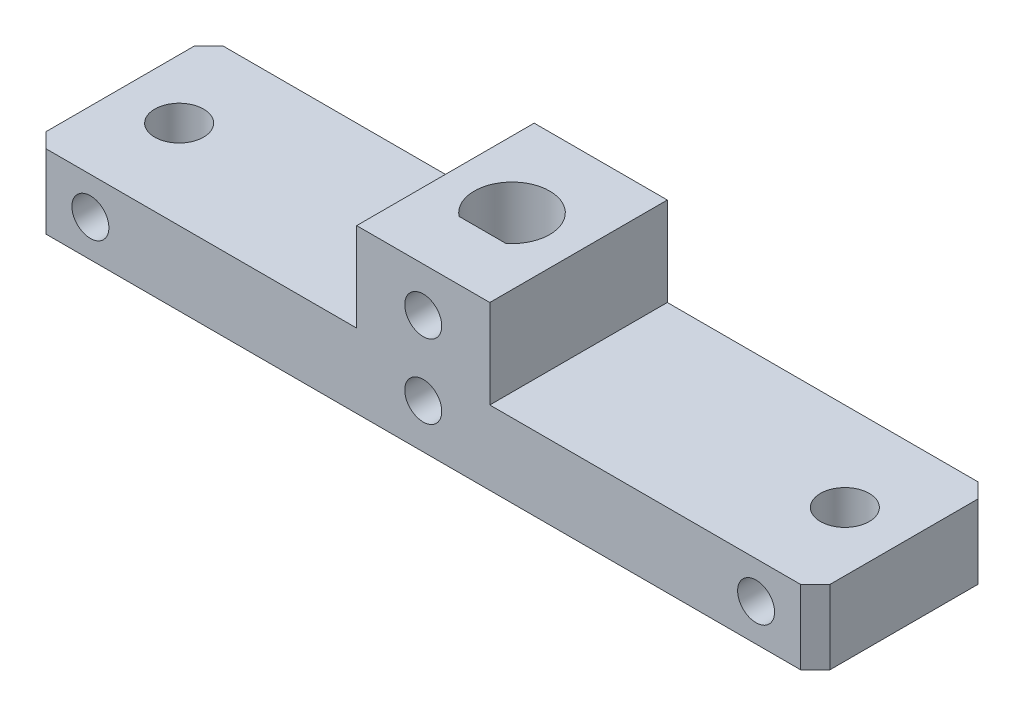
SolidWorks part; units mm, degrees
ref_plane "Top" through (0, 0, 0) normal (0, 0, 1) x (1, 0, 0)
ref_plane "Front" through (0, 0, 0) normal (0, 1, 0) x (1, 0, 0)
ref_plane "Right" through (0, 0, 0) normal (1, 0, 0) x (0, 0, -1)
sketch "Body Sketch" plane through (0, 0, 0) normal (0, 0, 1) x (1, 0, 0)
  line L0 (-26.5, 0) -> (26.5, 0)
  line L1 (26.5, 0) -> (26.5, 5)
  line L2 (26.5, 5) -> (4.5, 5)
  line L3 (4.5, 5) -> (4.5, 11)
  line L4 (4.5, 11) -> (-4.5, 11)
  line L5 (-4.5, 11) -> (-4.5, 5)
  line L6 (-4.5, 5) -> (-26.5, 5)
  line L7 (-26.5, 5) -> (-26.5, 0)
  point P8 (0, 0)
  dimension "D1" = 53
  dimension "D2" = 9
  dimension "D3" = 5
  dimension "D4" = 6
extrude "Body Extrude" add sketch "Body Sketch" against normal blind 12
sketch "Sketch2" plane through (0, 0, 0) normal (0, 1, 0) x (1, 0, 0)
  line L0 (-22.5, 6) -> (22.5, 6) construction
  line L1 (-1.5819, 4) -> (1.5819, 4)
  line L2 (0, 4) -> (0, 8.55) construction
  arc A2 (1.5819, 4) -> (-1.5819, 4) centre (0, 6) ccw
  point P8 (0, 6)
  dimension "D3" = 5.1
  dimension "D1" = 6
  dimension "D2" = 45
  dimension "D4" = 4.55
hole_wizard "M4x0.7 Tapped Hole6" positions "Sketch5" profile "Sketch6" tap size "M4x0.7" standard "ANSI Metric" end condition up to next
sketch "Sketch5" plane through (0, 0, 0) normal (0, 1, 0) x (1, 0, 0)
  line L0 (-22.5, 6) -> (22.5, 6) construction
  line L2 (0, 0) -> (0, 6) construction
  point P0 (-22.5, 6)
  point P2 (22.5, 6)
  dimension "D1" = 45
  dimension "D2" = 6
cosmetic thread "Hole Thread1"
cosmetic thread "Hole Thread2"
sketch "Sketch6" plane through (-22.5, 0, -6) normal (1, 0, 0) x (0, 0, -1)
  line L0 (0, 0) -> (0, 5)
  line L1 (0, 5) -> (1.65, 5)
  line L2 (1.65, 5) -> (1.65, 0)
  line L5 (1.65, 0) -> (0, 0)
  line L11 (0, -6.35) -> (0, 107.95) construction
  dimension "Thru Tap Drill Dia." = 3.3
  dimension "Thru Tap Drill Depth" = 5
extrude "Cut-Extrude1" cut sketch "Sketch2" along normal through all
hole_wizard "M3x0.5 Tapped Hole1" positions "Sketch7" profile "Sketch8" tap size "M3x0.5" standard "ANSI Metric" end condition up to next
sketch "Sketch7" plane through (0, 0, 0) normal (0, 0, 1) x (1, 0, 0)
  line L0 (-26.5, 5) -> (-26.5, 0) construction
  line L1 (-26.5, 2.5) -> (26.5, 2.5) construction
  line L2 (26.5, 0) -> (26.5, 5) construction
  line L4 (0, 0) -> (0, 11) construction
  line L5 (4.5, 11) -> (-4.5, 11) construction
  point P0 (-22.5, 2.5)
  point P2 (22.5, 2.5)
  point P4 (0, 8)
  point P6 (0, 3)
  dimension "D1" = 3
  dimension "D2" = 3
  dimension "D3" = 45
sketch "Sketch8" plane through (-22.5, 2.5, 0) normal (1, 0, 0) x (0, -1, 0)
  line L0 (0, 0) -> (0, 4.35)
  line L1 (0, 4.35) -> (1.25, 4.35)
  line L2 (1.25, 4.35) -> (1.25, 0)
  line L5 (1.25, 0) -> (0, 0)
  line L11 (0, -6.35) -> (0, 107.95) construction
  dimension "Thru Tap Drill Dia." = 2.5
  dimension "Thru Tap Drill Depth" = 4.35
cosmetic thread "Hole Thread3"
cosmetic thread "Hole Thread4"
cosmetic thread "Hole Thread5"
cosmetic thread "Hole Thread6"
chamfer "Chamfer1" distance 1 angle 45 4 edges at (-26.5, 2.5, -12) (-26.5, 2.5, 0) (26.5, 2.5, -12) (26.5, 2.5, 0)
equation "\"Height\"= 12mm"
equation "\"D1@Body Extrude\"=\"Height\""
equation "\"D1@Sketch2\"=0.5*\"Height\""
equation "\"D2@Sketch5\"=0.5*\"Height\""
